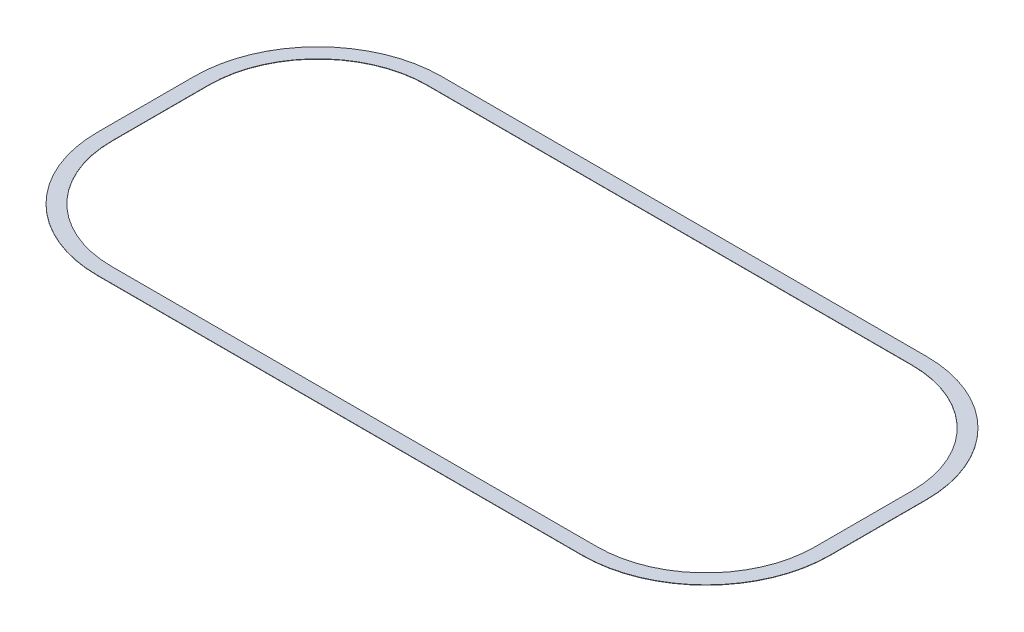
SolidWorks part; units mm, degrees
ref_plane "Front Plane" through (0, 0, 0) normal (0, 0, 1) x (1, 0, 0)
ref_plane "Top Plane" through (0, 0, 0) normal (0, 1, 0) x (1, 0, 0)
ref_plane "Right Plane" through (0, 0, 0) normal (1, 0, 0) x (0, 0, -1)
sketch "Sketch1" plane through (0, 0, 0) normal (0, 1, 0) x (1, 0, 0)
  line L0 (0, 0) -> (83820, 0)
  line L1 (105164.5877, 21344.5877) -> (105164.5877, 38108.5877)
  line L2 (83820, 59453.1755) -> (0, 59453.1755)
  line L3 (-21344.5877, 38108.5877) -> (-21344.5877, 21344.5877)
  line L4 (0, 2540) -> (83820, 2540)
  line L5 (102624.5877, 21344.5877) -> (102624.5877, 38108.5877)
  line L6 (83820, 56913.1755) -> (0, 56913.1755)
  line L7 (-18804.5877, 38108.5877) -> (-18804.5877, 21344.5877)
  arc A0 (83820, 0) -> (105164.5877, 21344.5877) centre (83820, 21344.5877) ccw
  arc A1 (105164.5877, 38108.5877) -> (83820, 59453.1755) centre (83820, 38108.5877) ccw
  arc A2 (0, 59453.1755) -> (-21344.5877, 38108.5877) centre (0, 38108.5877) ccw
  arc A3 (-21344.5877, 21344.5877) -> (0, 0) centre (0, 21344.5877) ccw
  arc A4 (83820, 2540) -> (102624.5877, 21344.5877) centre (83820, 21344.5877) ccw
  arc A5 (102624.5877, 38108.5877) -> (83820, 56913.1755) centre (83820, 38108.5877) ccw
  arc A6 (0, 56913.1755) -> (-18804.5877, 38108.5877) centre (0, 38108.5877) ccw
  arc A7 (-18804.5877, 21344.5877) -> (0, 2540) centre (0, 21344.5877) ccw
  dimension "D3" = 33528
  dimension "D4" = 33528
  dimension "D1" = 83820
  dimension "D2" = 16764
  dimension "D5" = 83820
  dimension "D6" = 33528
  dimension "D7" = 2540
extrude "Boss-Extrude1" add sketch "Sketch1" along normal blind 50.8
